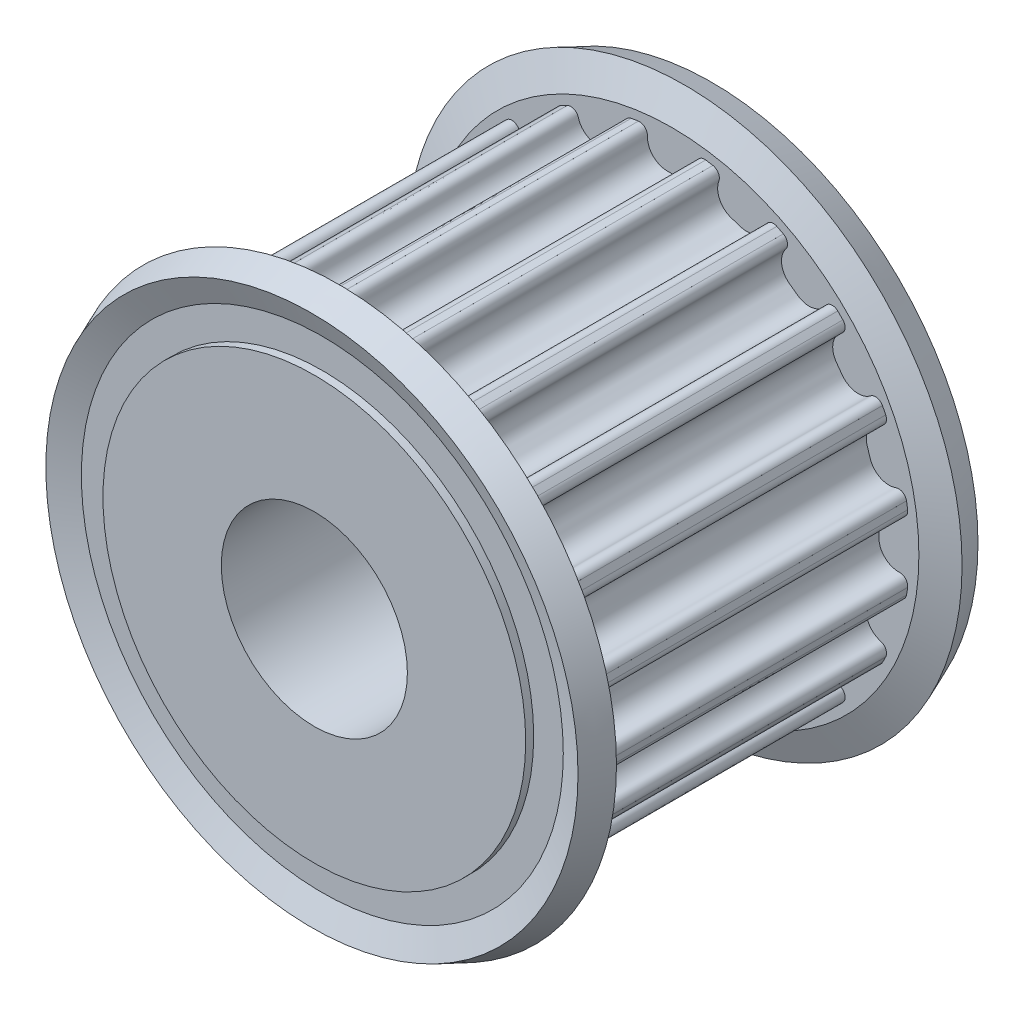
SolidWorks part; units mm, degrees
ref_plane "Спереди" through (0, 0, 0) normal (0, 0, 1) x (1, 0, 0)
ref_plane "Сверху" through (0, 0, 0) normal (0, 1, 0) x (1, 0, 0)
ref_plane "Справа" through (0, 0, 0) normal (1, 0, 0) x (0, 0, -1)
ref_axis "Ось1" through (0, 0, 50) along (0, 0, -1)
sketch "SketchRevolveGearBelt01" plane through (0, 0, 0) normal (1, 0, 0) x (0, 0, -1)
  line L0 (0, 0) -> (1, 0) construction
  line L1 (12.74, 0) -> (12.74, 13.6295)
  line L2 (12.74, 13.6295) -> (12.2244, 13.6295)
  line L3 (12.2244, 13.6295) -> (12.2244, 15.5381)
  line L4 (12.2244, 15.5381) -> (12.8953, 17.1579)
  line L5 (12.8953, 17.1579) -> (11.1424, 17.884)
  line L6 (11.1424, 17.884) -> (10.327, 15.9155)
  line L7 (10.327, 15.9155) -> (10.327, 15.344)
  line L8 (10.327, 15.344) -> (-10.327, 15.344)
  line L9 (-10.327, 15.344) -> (-10.327, 15.9155)
  line L10 (-10.327, 15.9155) -> (-11.1424, 17.884)
  line L11 (-11.1424, 17.884) -> (-12.8953, 17.1579)
  line L12 (-12.8953, 17.1579) -> (-12.2244, 15.5381)
  line L13 (-12.2244, 15.5381) -> (-12.2244, 13.6295)
  line L14 (-12.2244, 13.6295) -> (-12.74, 13.6295)
  line L15 (-12.74, 13.6295) -> (-12.74, 0)
  line L16 (-12.74, 0) -> (12.74, 0)
  dimension "GearBeltFlange1OutsideLength" = 1.9086
  dimension "GearBeltFlange1X" = 0.6709
  dimension "GearBeltFlange1Y" = 1.6198
  dimension "GearBeltFlangeThickness" = 1.8974
  dimension "GearBeltFlangeInside" = 0.5715
  dimension "GearBeltOutsideDiameter" = 15.344
  dimension "GearBeltFlange2X" = 0.6709
  dimension "D1" = 25.48
revolve "GearBelt01" add sketch "SketchRevolveGearBelt01" angle 360 about L0
sketch "SketchToothGearBelt01" plane through (0, 0, 0) normal (0, 0, 1) x (1, 0, 0)
  line L0 (15.7555, 2.2509) -> (15.1892, 2.17)
  line L1 (15.1892, -2.17) -> (15.7555, -2.2509)
  arc A2 (15.7555, -2.2509) -> (15.7555, 2.2509) centre (0, 0) ccw
  circle A3 centre (0, 0) radius 15.9155 construction
  spline S0 degree 3 poles (15.1892, -2.17) (15.1933, -2.1413) (15.1958, -2.0978) (15.1916, -2.0399) (15.1848, -1.997) (15.1743, -1.9547) (15.1603, -1.9136) (15.1428, -1.8738) (15.1219, -1.8356) (15.0979, -1.7993) (15.0709, -1.7653) (15.041, -1.7336) (15.0086, -1.7046) (14.9738, -1.6785) (14.9369, -1.6555) (14.8981, -1.6357) (14.8578, -1.6193) (14.8163, -1.6064) (14.7738, -1.5971) (14.7307, -1.5914) (14.6736, -1.5894) (14.5978, -1.5908) (14.5033, -1.5873) (14.4043, -1.5753) (14.3065, -1.5557) (14.2106, -1.5285) (14.1171, -1.4939) (14.0266, -1.452) (13.9397, -1.4032) (13.8569, -1.3477) (13.7786, -1.2859) (13.7055, -1.2181) (13.6379, -1.1449) (13.5762, -1.0665) (13.5209, -0.9836) (13.4722, -0.8965) (13.4305, -0.806) (13.396, -0.7124) (13.369, -0.6164) (13.3496, -0.5186) (13.3376, -0.4196) (13.3342, -0.2999) (13.3356, -0.16) (13.3351, 0) (13.3356, 0.16) (13.3342, 0.2999) (13.3376, 0.4196) (13.3496, 0.5186) (13.369, 0.6164) (13.396, 0.7124) (13.4305, 0.806) (13.4722, 0.8965) (13.5209, 0.9836) (13.5762, 1.0665) (13.6379, 1.1449) (13.7055, 1.2181) (13.7786, 1.2859) (13.8569, 1.3477) (13.9397, 1.4032) (14.0266, 1.452) (14.1171, 1.4939) (14.2106, 1.5285) (14.3065, 1.5557) (14.4043, 1.5753) (14.5033, 1.5873) (14.5978, 1.5908) (14.6736, 1.5894) (14.7307, 1.5914) (14.7738, 1.5971) (14.8163, 1.6064) (14.8578, 1.6193) (14.8981, 1.6357) (14.9369, 1.6555) (14.9738, 1.6785) (15.0086, 1.7046) (15.041, 1.7336) (15.0709, 1.7653) (15.0979, 1.7993) (15.1219, 1.8356) (15.1428, 1.8738) (15.1603, 1.9136) (15.1743, 1.9547) (15.1848, 1.997) (15.1916, 2.0399) (15.1958, 2.0978) (15.1933, 2.1413) (15.1892, 2.17) knots 0 0 0 0 0.013305 0.019957 0.026609 0.033261 0.039914 0.046566 0.053218 0.059871 0.066523 0.073175 0.079828 0.08648 0.093132 0.099784 0.106437 0.113089 0.119741 0.126394 0.133046 0.145958 0.16121 0.176462 0.191714 0.206966 0.222218 0.23747 0.252722 0.267974 0.283226 0.298478 0.31373 0.328983 0.344235 0.359487 0.374739 0.389991 0.405243 0.420495 0.435747 0.450999 0.4755 0.5 0.5245 0.549001 0.564253 0.579505 0.594757 0.610009 0.625261 0.640513 0.655765 0.671017 0.68627 0.701522 0.716774 0.732026 0.747278 0.76253 0.777782 0.793034 0.808286 0.823538 0.83879 0.854042 0.866954 0.873606 0.880259 0.886911 0.893563 0.900216 0.906868 0.91352 0.920172 0.926825 0.933477 0.940129 0.946782 0.953434 0.960086 0.966739 0.973391 0.980043 0.986695 1 1 1 1
extrude "ToothExtrudeCutGearBelt01" cut sketch "SketchToothGearBelt01" against normal blind 10.327 and the other way blind 10.327
pattern_circular "PatternGearBelt01" count 20 every 18 about axis through (0, 0, 50) along (0, 0, -1) of "ToothExtrudeCutGearBelt01"
sketch "BoreRevolveSketch" plane through (0, 0, 0) normal (1, 0, 0) x (0, 0, -1)
  line L0 (0, 0) -> (1, 0) construction
  line L1 (-12.8953, 0) -> (12.8953, 0)
  line L2 (12.8953, 0) -> (12.8953, 6)
  line L3 (12.8953, 6) -> (-12.8953, 6)
  line L4 (-12.8953, 6) -> (-12.8953, 0)
  line L5 (12.8953, 17.1579) -> (12.8953, -17.1579) construction
  line L6 (-12.8953, 17.1579) -> (-12.8953, -17.1579) construction
  dimension "TaperSide1" = 6
  dimension "TaperSide2" = 6
revolve "BoreRevolveCut" cut sketch "BoreRevolveSketch" angle 360 about L0
